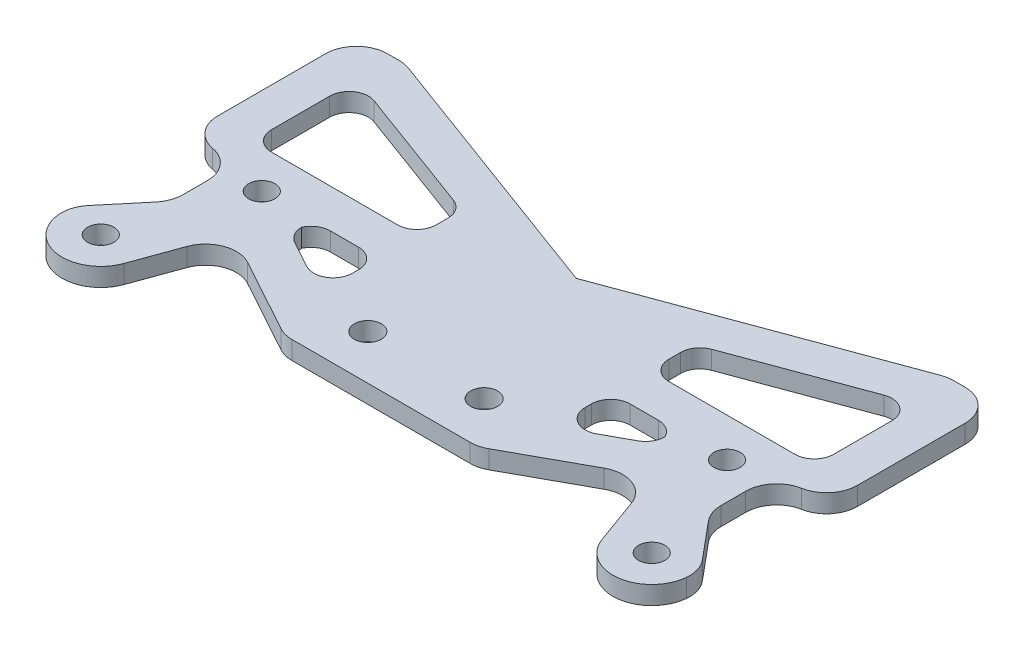
SolidWorks part; units mm, degrees
material "Custom Plastic"
ref_plane "Front Plane" through (0, 0, 0) normal (0, 0, 1) x (1, 0, 0)
ref_plane "Top Plane" through (0, 0, 0) normal (0, 1, 0) x (1, 0, 0)
ref_plane "Right Plane" through (0, 0, 0) normal (1, 0, 0) x (0, 0, -1)
sketch "Sketch1" plane through (0, 0, 0) normal (0, 1, 0) x (1, 0, 0)
  line L1 (-52.3875, -31.75) -> (52.3875, -31.75)
  line L2 (-52.3875, -31.75) -> (-52.3875, 31.75)
  line L3 (-52.3875, 31.75) -> (52.3875, 31.75)
  line L4 (52.3875, -31.75) -> (52.3875, 31.75)
  line L5 (-52.3875, -31.75) -> (52.3875, 31.75) construction
  line L6 (-52.3875, 31.75) -> (52.3875, -31.75) construction
  point P0 (0, 0)
  dimension "D1" = 104.775
  dimension "D2" = 63.5
extrude "Base" add sketch "Sketch1" along normal blind 3
sketch "Sketch2" plane through (0, 3, 0) normal (0, 1, 0) x (1, 0, 0)
  line L0 (-44.45, 31.75) -> (0, 15.3521)
  line L1 (52.3875, 31.75) -> (-52.3875, 31.75) construction
  line L2 (0, 15.3521) -> (44.45, 31.75)
  line L3 (-44.45, 31.75) -> (44.45, 31.75)
  line L4 (0, 0) -> (0, 31.75) construction
  circle A0 centre (0, 23.8125) radius 7.9375 construction
  dimension "D1" = 15.875
  dimension "D2" = 88.9
  dimension "D3" = 7.9375
extrude "Tube notch" cut sketch "Sketch2" against normal through all
sketch "Sketch11" plane through (0, 3, 0) normal (0, 1, 0) x (1, 0, 0)
  circle A0 centre (-9.525, -9.2582) radius 2.2099
  circle A1 centre (9.525, -9.2582) radius 2.2099
  arc A3 (9.525, -11.4681) -> (9.525, -7.0483) centre (9.525, -9.2582) ccw construction
  arc A4 (-9.525, -7.0483) -> (-9.525, -11.4681) centre (-9.525, -9.2582) ccw construction
  point P1 (9.525, -9.2582)
extrude "Cut-Extrude1" cut sketch "Sketch11" against normal through all
sketch "Sketch13" plane through (0, 3, 0) normal (0, 1, 0) x (1, 0, 0)
  line L0 (0, 27.9748) -> (0, -39.0936) construction
  line L1 (-38.1, 1.9516) -> (38.1, 1.9516) construction
  line L2 (-45.1148, -17.4017) -> (45.1148, -17.4017) construction
  point P7 (-38.1, 1.9516)
  point P8 (-45.1148, -17.4017)
  point P11 (0, -17.4017)
  point P12 (0, 1.9516)
hole_wizard "#8 Clearance Hole1" positions "Sketch15" profile "Sketch14" hole size "#8" standard "ANSI Inch" end condition through all
sketch "Sketch15" plane through (0, 3, 0) normal (0, 1, 0) x (1, 0, 0)
  point P0 (-38.1, 1.9516)
  point P3 (-45.1148, -17.4017)
  point P6 (45.1148, -17.4017)
  point P9 (38.1, 1.9516)
sketch "Sketch14" plane through (-38.1, 3, -1.9516) normal (1, 0, 0) x (0, 0, 1)
  line L0 (0, 0) -> (0, 3)
  line L1 (0, 3) -> (2.1526, 3)
  line L2 (2.1526, 3) -> (2.1526, 0)
  line L5 (2.1526, 0) -> (0, 0)
  line L11 (0, -6.35) -> (0, 107.95) construction
  dimension "Thru Hole Dia." = 4.3053
  dimension "Thru Hole Depth" = 3
sketch "Sketch16" plane through (0, 3, 0) normal (0, 1, 0) x (1, 0, 0)
  line L0 (-52.3875, -31.75) -> (-52.3875, 4.1155)
  line L2 (-51.0847, -15.2378) -> (-44.0699, -6.8324)
  line L3 (-39.1448, -19.5655) -> (-34.3847, -6.4325)
  line L4 (-34.3847, -6.4325) -> (-15.875, -16.5925)
  line L5 (-15.875, -16.5925) -> (0, -16.5925)
  line L6 (0, 33.1739) -> (0, -41.3466) construction
  line L7 (-51.0847, -15.2378) -> (-45.1148, -17.4017) construction
  line L8 (-45.1148, -17.4017) -> (-39.1448, -19.5655) construction
  line L9 (-44.0699, 4.1155) -> (-38.1, 1.9516) construction
  line L10 (-38.1, 1.9516) -> (-32.1301, -0.2123) construction
  line L12 (0, -16.5925) -> (0, -31.75)
  line L13 (0, -31.75) -> (-52.3875, -31.75)
  line L14 (-44.0699, -6.8324) -> (-44.0699, 4.1155)
  line L15 (-52.3875, -31.75) -> (52.3875, -31.75) construction
  line L16 (-44.0699, 4.1155) -> (-52.3875, 4.1155)
  line L17 (-52.3875, 31.75) -> (-52.3875, -31.75) construction
  arc A0 (-51.0847, -15.2378) -> (-39.1448, -19.5655) centre (-45.1148, -17.4017) ccw
  circle A2 centre (-9.525, -9.2582) radius 2.2099 construction
  dimension "D2" = 7.3343
  dimension "D1" = 6.35
  dimension "D3" = 31.75
  dimension "D4" = 10.16
extrude "Cut-Extrude2" cut sketch "Sketch16" against normal through all
mirror "Mirror1" about plane through (0, 0, 16.5925) normal (1, 0, 0) of "Cut-Extrude2"
fillet "Fillet1" radius 5.08 14 edges at (44.45, 1.5, -31.75) (52.3875, 1.5, -31.75) (34.3847, 1.5, 6.4325) (15.875, 1.5, 16.5925) (-15.875, 1.5, 16.5925) (-34.3847, 1.5, 6.4325) (-44.45, 1.5, -31.75) (-52.3875, 1.5, -31.75) (51.0847, 1.5, 15.2378) (44.0699, 1.5, 6.8324) (44.0699, 1.5, -4.1155) (-51.0847, 1.5, 15.2378) (-44.0699, 1.5, 6.8324) (-44.0699, 1.5, -4.1155)
fillet "Fillet2" radius 5.08 2 edges at (52.3875, 1.5, -4.1155) (-52.3875, 1.5, -4.1155)
sketch "Sketch17" plane through (0, 3, 0) normal (0, 1, 0) x (1, 0, 0)
  line L0 (-19.05, -14.8498) -> (-19.05, 22.3798) construction
  line L1 (-17.0168, -15.9658) -> (-29.1854, -9.2864) construction
  line L2 (-43.5989, 31.436) -> (0, 15.3521) construction
  line L3 (0, 0) -> (-19.05, 0) construction
  line L4 (0, 15.3521) -> (43.5989, 31.436) construction
  line L5 (19.05, 22.3798) -> (19.05, -14.8498) construction
  line L6 (17.0168, -15.9658) -> (29.1854, -9.2864) construction
  line L7 (0, 0) -> (19.05, 0) construction
  line L8 (-19.05, 8.3016) -> (-52.3875, 8.3016) construction
  line L9 (-52.3875, 26.67) -> (-52.3875, 9.027) construction
  line L10 (-19.05, -7.6061) -> (-36.4623, 1.9516) construction
  line L11 (-19.05, 15.6115) -> (-46.0375, 25.5673) construction
  line L12 (-46.0375, 25.5673) -> (-46.0375, 8.3016) construction
  line L13 (-46.0375, 8.3016) -> (-46.0375, 25.5673)
  line L14 (-46.0375, 25.5673) -> (-19.05, 15.6115)
  line L15 (-19.05, 15.6115) -> (-19.05, 8.3016)
  line L16 (-19.05, 8.3016) -> (-46.0375, 8.3016)
  line L17 (0, 25.5673) -> (0, -31.2785) construction
  line L18 (46.0375, 25.5673) -> (46.0375, 8.3016) construction
  line L19 (19.05, 15.6115) -> (46.0375, 25.5673) construction
  line L20 (19.05, 8.3016) -> (46.0375, 8.3016)
  line L21 (19.05, 15.6115) -> (19.05, 8.3016)
  line L22 (46.0375, 25.5673) -> (19.05, 15.6115)
  line L23 (46.0375, 8.3016) -> (46.0375, 25.5673)
  line L24 (-19.05, 1.9516) -> (-36.4623, 1.9516) construction
  line L25 (-29.5973, 1.9516) -> (-19.05, 1.9516)
  line L26 (-19.05, 1.9516) -> (-19.05, -7.6061)
  line L27 (-19.05, -7.6061) -> (-30.2993, -1.4313)
  line L28 (19.05, -7.6061) -> (30.2993, -1.4313)
  line L29 (19.05, 1.9516) -> (19.05, -7.6061)
  line L30 (29.5973, 1.9516) -> (19.05, 1.9516)
  circle A0 centre (-38.1, 1.9516) radius 2.1526 construction
  arc A1 (-29.5973, 1.9516) -> (-30.2993, -1.4313) centre (-38.1, 1.9516) cw
  arc A2 (29.5973, 1.9516) -> (30.2993, -1.4313) centre (38.1, 1.9516) ccw
  point P26 (-52.3875, 17.8485)
  dimension "D2" = 6.35
  dimension "D7" = 6.35
  dimension "D1" = 38.1
  dimension "D3" = 6.35
  dimension "D4" = 6.35
  dimension "D5" = 6.35
  dimension "D6" = 6.35
extrude "Cut-Extrude3" cut sketch "Sketch17" against normal through all
fillet "Fillet3" radius 3.175 16 edges at (46.0375, 1.5, -25.5673) (46.0375, 1.5, -8.3016) (-19.05, 1.5, -8.3016) (-19.05, 1.5, -15.6115) (-46.0375, 1.5, -25.5673) (19.05, 1.5, -15.6115) (19.05, 1.5, -8.3016) (-46.0375, 1.5, -8.3016) (-19.05, 1.5, -1.9516) (-19.05, 1.5, 7.6061) (-30.2993, 1.5, 1.4313) (-29.5973, 1.5, -1.9516) (30.2993, 1.5, 1.4313) (29.5973, 1.5, -1.9516) (19.05, 1.5, 7.6061) (19.05, 1.5, -1.9516)
equation "\"MAT_THICKNESS\"=0.1"
